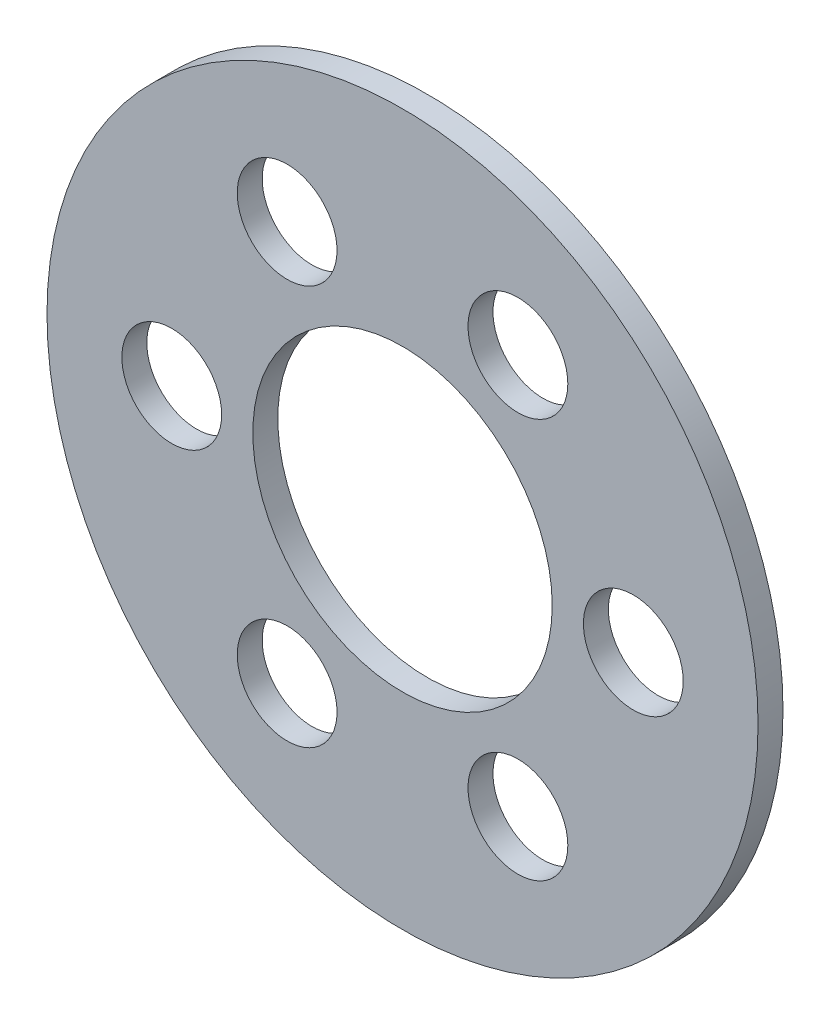
SolidWorks part; units mm, degrees
ref_plane "Ebene vorne" through (0, 0, 0) normal (0, 0, 1) x (1, 0, 0)
ref_plane "Ebene oben" through (0, 0, 0) normal (0, 1, 0) x (1, 0, 0)
ref_plane "Ebene rechts" through (0, 0, 0) normal (1, 0, 0) x (0, 0, -1)
sketch "Skizze1" plane through (0, 0, 0) normal (0, 0, 1) x (1, 0, 0)
  line L0 (-6, 0) -> (-12.5, 0) construction
  circle A0 centre (0, 0) radius 6
  circle A1 centre (0, 0) radius 14.25
  circle A2 centre (0, 0) radius 12.5
  circle A3 centre (-9.25, 0) radius 2
  circle A4 centre (-4.625, 8.0107) radius 2
  circle A5 centre (4.625, 8.0107) radius 2
  circle A6 centre (9.25, 0) radius 2
  circle A7 centre (4.625, -8.0107) radius 2
  circle A8 centre (-4.625, -8.0107) radius 2
  point P21 (0, 0)
  dimension "D1" = 28.5
  dimension "D2" = 25
  dimension "D3" = 6
extrude "Aufsatz-Linear austragen1" add sketch "Skizze1" along normal blind 1 contours A0 A3 A2 A8 A7 A6 A5 A4 | A1 A2 region at (-13.8469, 0, 0) region at (-12.1464, 0, 0)
